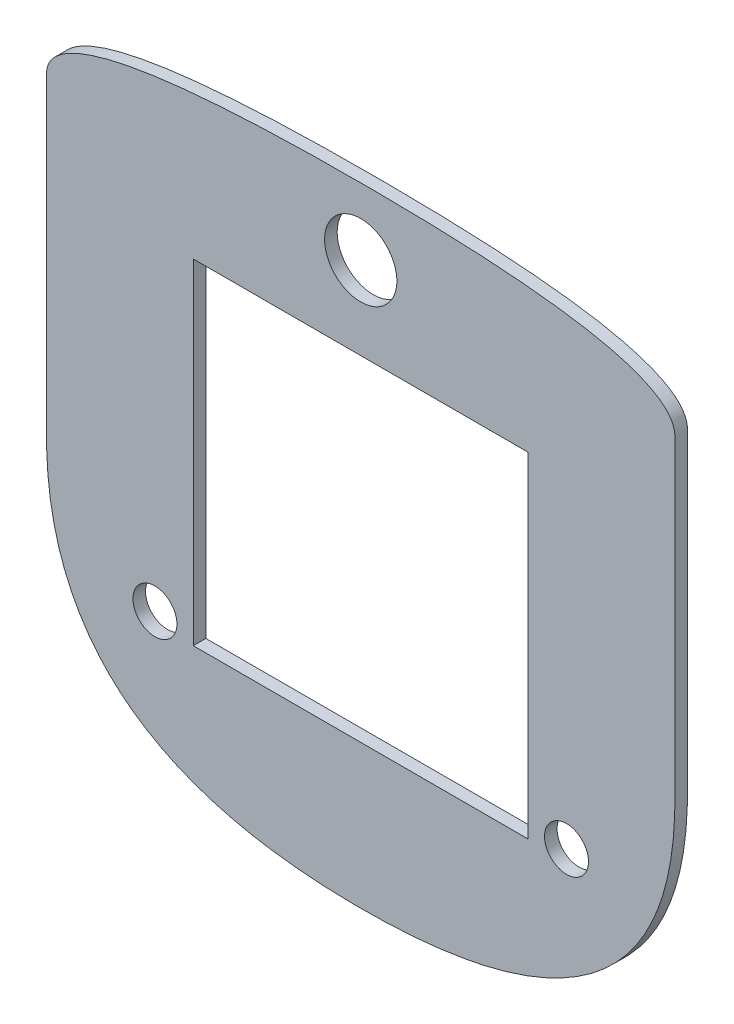
SolidWorks part; units mm, degrees
ref_plane "Front Plane" through (0, 0, 0) normal (0, 0, 1) x (1, 0, 0)
ref_plane "Top Plane" through (0, 0, 0) normal (0, 1, 0) x (1, 0, 0)
ref_plane "Right Plane" through (0, 0, 0) normal (1, 0, 0) x (0, 0, -1)
ref_plane "Plane1" through (0, 0, 650) normal (0, 0, -1) x (-1, 0, 0)
sketch "Sketch1" plane through (0, 0, 650) normal (0, 0, -1) x (-1, 0, 0)
  line L0 (0, 120) -> (0, -80) construction
  line L1 (0, 70.1122) -> (0, -75.0001) construction
  line L2 (-53.3, 72.35) -> (53.3, 72.35)
  line L3 (-53.3, 72.35) -> (-53.3, -34.25)
  line L4 (-53.3, -34.25) -> (53.3, -34.25)
  line L5 (53.3, 72.35) -> (53.3, -34.25)
  line L6 (-53.3, 72.35) -> (53.3, -34.25) construction
  line L7 (-53.3, -34.25) -> (53.3, 72.35) construction
  circle A0 centre (-65.5, -30.8878) radius 7
  circle A1 centre (65.5, -30.8878) radius 7
  circle A2 centre (0, 98.6502) radius 11.5
  spline S0 degree 3 poles (-100, 91.6667) (-100, 100.5541) (-99.8835, 101.663) (-99.344, 103.2464) (-98.4974, 104.6847) (-97.0622, 106.3843) (-94.8888, 108.1258) (-91.9976, 109.7782) (-88.9551, 111.1271) (-85.8262, 112.2552) (-82.6425, 113.2169) (-79.4227, 114.0479) (-76.1777, 114.7739) (-72.9147, 115.4129) (-69.6383, 115.979) (-65.2561, 116.6501) (-59.7591, 117.3544) (-53.1437, 118.032) (-46.5161, 118.5751) (-37.6683, 119.1501) (-26.5955, 119.6359) (-13.2992, 119.9414) (-4.4331, 120) (4.4331, 120) (13.2992, 119.9414) (26.5955, 119.6359) (37.6683, 119.1501) (46.5161, 118.5751) (53.1437, 118.032) (59.7591, 117.3544) (65.2561, 116.6501) (69.6383, 115.979) (72.9147, 115.4129) (76.1777, 114.7739) (79.4227, 114.0479) (82.6425, 113.2169) (85.8262, 112.2552) (88.9551, 111.1271) (91.9976, 109.7782) (94.8888, 108.1258) (97.0622, 106.3843) (98.4974, 104.6847) (99.344, 103.2464) (99.8835, 101.663) (100, 100.5541) (100, 91.6667) (100, 75) (100, 50) (100, 25) (100, 8.3333) (100, -3.0509) (99.7823, -9.1535) (98.6814, -18.2496) (96.6708, -27.1928) (93.6177, -35.841) (89.4261, -44.0037) (84.0794, -51.4648) (77.6729, -58.0369) (70.3884, -63.6161) (62.4486, -68.1997) (51.2385, -73.0758) (36.4788, -77.1218) (18.3084, -79.5568) (6.1019, -80) (-6.1019, -80) (-18.3084, -79.5568) (-36.4788, -77.1218) (-51.2385, -73.0758) (-62.4486, -68.1997) (-70.3884, -63.6161) (-77.6729, -58.0369) (-84.0794, -51.4648) (-89.4261, -44.0037) (-93.6177, -35.841) (-96.6708, -27.1928) (-98.6814, -18.2496) (-99.7823, -9.1535) (-100, -3.0509) (-100, 8.3333) (-100, 25) (-100, 50) (-100, 75) (-100, 91.6667) (-100, 100.5541) (-99.8835, 101.663) knots -0.070853 -0.035426 0 0 0.002356 0.004712 0.007067 0.009423 0.014135 0.018847 0.023558 0.02827 0.032982 0.037693 0.042405 0.047116 0.051828 0.05654 0.065963 0.075386 0.08481 0.094233 0.11308 0.131926 0.150773 0.150773 0.169619 0.188466 0.207313 0.216736 0.226159 0.235583 0.245006 0.249718 0.254429 0.259141 0.263853 0.268564 0.273276 0.277988 0.282699 0.287411 0.292123 0.294478 0.296834 0.29919 0.301546 0.301546 0.336972 0.372399 0.407825 0.443252 0.443252 0.456222 0.469192 0.482162 0.495132 0.508102 0.521072 0.534042 0.547012 0.559982 0.572952 0.598893 0.624833 0.650773 0.650773 0.676713 0.702653 0.728593 0.741563 0.754533 0.767504 0.780474 0.793444 0.806414 0.819384 0.832354 0.845324 0.858294 0.858294 0.893721 0.929147 0.964574 1 1 1.002356 1.004712 1.007067 only from (-100, 100) to (-100, 100)
  spline S1 degree 3 poles (-100, 91.6667) (-100, 100.5541) (-99.8835, 101.663) (-99.344, 103.2464) (-98.4974, 104.6847) (-97.0622, 106.3843) (-94.8888, 108.1258) (-91.9976, 109.7782) (-88.9551, 111.1271) (-85.8262, 112.2552) (-82.6425, 113.2169) (-79.4227, 114.0479) (-76.1777, 114.7739) (-72.9147, 115.4129) (-69.6383, 115.979) (-65.2561, 116.6501) (-59.7591, 117.3544) (-53.1437, 118.032) (-46.5161, 118.5751) (-37.6683, 119.1501) (-26.5955, 119.6359) (-13.2992, 119.9414) (-4.4331, 120) (4.4331, 120) (13.2992, 119.9414) (26.5955, 119.6359) (37.6683, 119.1501) (46.5161, 118.5751) (53.1437, 118.032) (59.7591, 117.3544) (65.2561, 116.6501) (69.6383, 115.979) (72.9147, 115.4129) (76.1777, 114.7739) (79.4227, 114.0479) (82.6425, 113.2169) (85.8262, 112.2552) (88.9551, 111.1271) (91.9976, 109.7782) (94.8888, 108.1258) (97.0622, 106.3843) (98.4974, 104.6847) (99.344, 103.2464) (99.8835, 101.663) (100, 100.5541) (100, 91.6667) (100, 75) (100, 50) (100, 25) (100, 8.3333) (100, -3.0509) (99.7823, -9.1535) (98.6814, -18.2496) (96.6708, -27.1928) (93.6177, -35.841) (89.4261, -44.0037) (84.0794, -51.4648) (77.6729, -58.0369) (70.3884, -63.6161) (62.4486, -68.1997) (51.2385, -73.0758) (36.4788, -77.1218) (18.3084, -79.5568) (6.1019, -80) (-6.1019, -80) (-18.3084, -79.5568) (-36.4788, -77.1218) (-51.2385, -73.0758) (-62.4486, -68.1997) (-70.3884, -63.6161) (-77.6729, -58.0369) (-84.0794, -51.4648) (-89.4261, -44.0037) (-93.6177, -35.841) (-96.6708, -27.1928) (-98.6814, -18.2496) (-99.7823, -9.1535) (-100, -3.0509) (-100, 8.3333) (-100, 25) (-100, 50) (-100, 75) (-100, 91.6667) (-100, 100.5541) (-99.8835, 101.663) knots -0.070853 -0.035426 0 0 0.002356 0.004712 0.007067 0.009423 0.014135 0.018847 0.023558 0.02827 0.032982 0.037693 0.042405 0.047116 0.051828 0.05654 0.065963 0.075386 0.08481 0.094233 0.11308 0.131926 0.150773 0.150773 0.169619 0.188466 0.207313 0.216736 0.226159 0.235583 0.245006 0.249718 0.254429 0.259141 0.263853 0.268564 0.273276 0.277988 0.282699 0.287411 0.292123 0.294478 0.296834 0.29919 0.301546 0.301546 0.336972 0.372399 0.407825 0.443252 0.443252 0.456222 0.469192 0.482162 0.495132 0.508102 0.521072 0.534042 0.547012 0.559982 0.572952 0.598893 0.624833 0.650773 0.650773 0.676713 0.702653 0.728593 0.741563 0.754533 0.767504 0.780474 0.793444 0.806414 0.819384 0.832354 0.845324 0.858294 0.858294 0.893721 0.929147 0.964574 1 1 1.002356 1.004712 1.007067 only from (-100, 100) to (-100, 100)
  spline S2 degree 3 poles (-100, 100.5541) (-100, 91.6667) (-100, 75) (-100, 50) (-100, 25) (-100, 8.3333) (-100, -3.0509) (-99.7823, -9.1535) (-98.6814, -18.2496) (-96.6708, -27.1928) (-93.6177, -35.841) (-89.4261, -44.0037) (-84.0794, -51.4648) (-77.6729, -58.0369) (-70.3884, -63.6161) (-62.4486, -68.1997) (-51.2385, -73.0758) (-36.4788, -77.1218) (-18.3084, -79.5568) (-6.1019, -80) (6.1019, -80) (18.3084, -79.5568) (36.4788, -77.1218) (51.2385, -73.0758) (62.4486, -68.1997) (70.3884, -63.6161) (77.6729, -58.0369) (84.0794, -51.4648) (89.4261, -44.0037) (93.6177, -35.841) (96.6708, -27.1928) (98.6814, -18.2496) (99.7823, -9.1535) (100, -3.0509) (100, 8.3333) (100, 25) (100, 50) (100, 75) (100, 91.6667) (100, 100.5541) (99.8835, 101.663) (99.344, 103.2464) (98.4974, 104.6847) (97.0622, 106.3843) (94.8888, 108.1258) (91.9976, 109.7782) (88.9551, 111.1271) (85.8262, 112.2552) (82.6424, 113.2169) (79.4227, 114.0479) (76.1777, 114.7739) (72.9147, 115.4129) (69.6383, 115.979) (65.2561, 116.6501) (59.7591, 117.3544) (53.1437, 118.032) (46.5161, 118.5751) (37.6683, 119.1501) (26.5955, 119.6359) (13.2992, 119.9414) (4.4331, 120) (-4.4331, 120) (-13.2992, 119.9414) (-26.5955, 119.6359) (-37.6683, 119.1501) (-46.5161, 118.5751) (-53.1437, 118.032) (-59.7591, 117.3544) (-65.2561, 116.6501) (-69.6383, 115.979) (-72.9147, 115.4129) (-76.1777, 114.7739) (-79.4227, 114.0479) (-82.6424, 113.2169) (-85.8262, 112.2552) (-88.9551, 111.1271) (-91.9976, 109.7782) (-94.8888, 108.1258) (-97.0622, 106.3843) (-98.4974, 104.6847) (-99.344, 103.2464) (-99.8835, 101.663) (-100, 100.5541) (-100, 91.6667) (-100, 75) knots -0.004712 -0.002356 0 0 0.035426 0.070853 0.106279 0.141706 0.141706 0.154676 0.167646 0.180616 0.193586 0.206556 0.219526 0.232496 0.245467 0.258437 0.271407 0.297347 0.323287 0.349227 0.349227 0.375167 0.401107 0.427048 0.440018 0.452988 0.465958 0.478928 0.491898 0.504868 0.517838 0.530808 0.543778 0.556748 0.556748 0.592175 0.627601 0.663028 0.698454 0.698454 0.70081 0.703166 0.705522 0.707877 0.712589 0.717301 0.722012 0.726724 0.731436 0.736147 0.740859 0.745571 0.750282 0.754994 0.764417 0.773841 0.783264 0.792687 0.811534 0.830381 0.849227 0.849227 0.868074 0.88692 0.905767 0.91519 0.924614 0.934037 0.94346 0.948172 0.952884 0.957595 0.962307 0.967018 0.97173 0.976442 0.981153 0.985865 0.990577 0.992933 0.995288 0.997644 1 1 1.035426 1.070853 1.106279 only from (-100, 100) to (-100, 100) construction
  point P13 (0, 19.05)
  point P18 (0, 15.7732)
  point P21 (0, 19.1063)
  dimension "D1" = 14
  dimension "D2" = 23
  dimension "D3" = 106.6
  dimension "D4" = 19.05
extrude "Boss-Extrude1" add sketch "Sketch1" against normal blind 4
